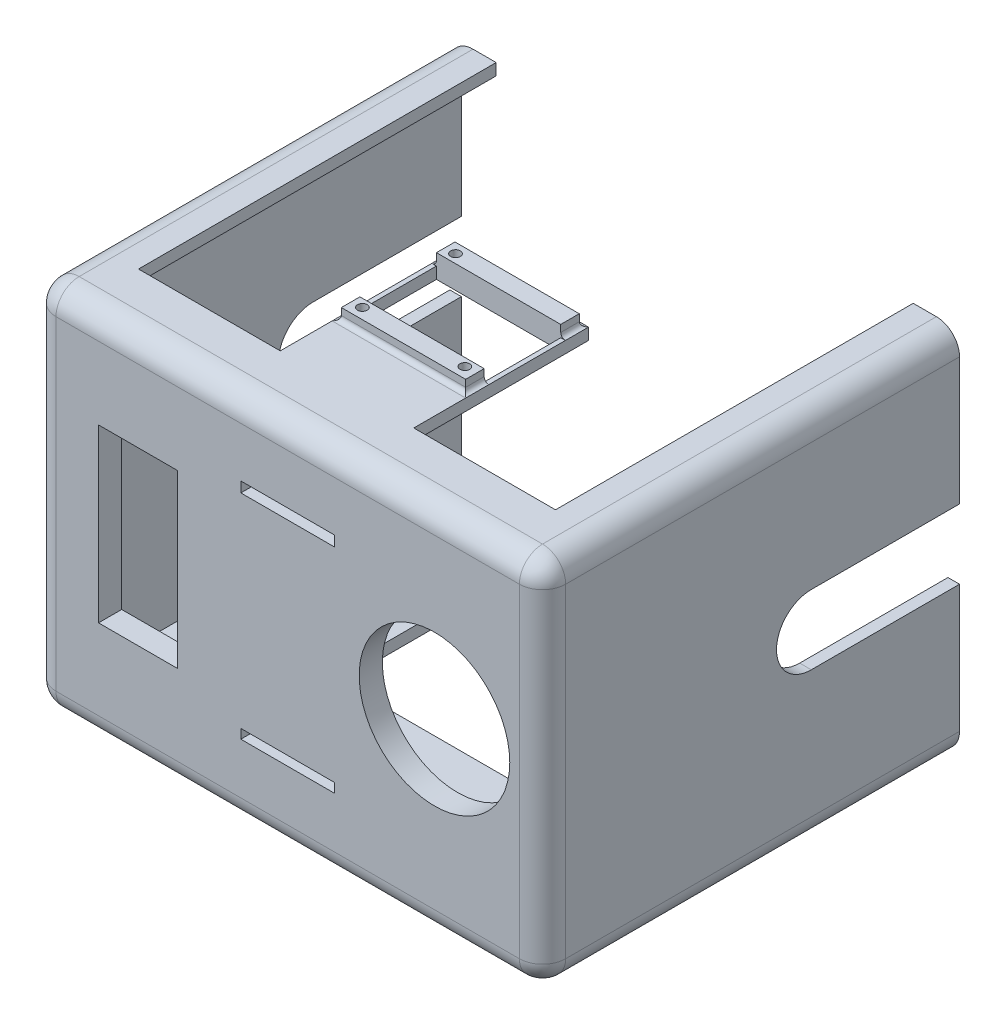
SolidWorks part; units mm, degrees
ref_plane "Plan de face" through (0, 0, 0) normal (0, 0, 1) x (1, 0, 0)
ref_plane "Plan de dessus" through (0, 0, 0) normal (0, 1, 0) x (1, 0, 0)
ref_plane "Plan de droite" through (0, 0, 0) normal (1, 0, 0) x (0, 0, -1)
sketch "Esquisse1" plane through (0, 0, 0) normal (0, 1, 0) x (1, 0, 0)
  line L1 (-48.5287, 46.8615) -> (61.4713, 46.8615)
  line L2 (-48.5287, 46.8615) -> (-48.5287, -53.1385)
  line L3 (-48.5287, -53.1385) -> (61.4713, -53.1385)
  line L4 (61.4713, 46.8615) -> (61.4713, -53.1385)
  point P10 (-45.5809, 46.8615)
  point P11 (-10.7604, 46.8615)
  point P12 (-6.0287, 46.8615)
  point P13 (13.9713, 46.8615)
  point P14 (27.7429, 46.8615)
  point P15 (44.6509, 46.8615)
  dimension "D1" = 100
  dimension "D2" = 110
extrude "Boss.-Extru.1" add sketch "Esquisse1" along normal blind 80
sketch "Esquisse3" plane through (0, 0, -46.8615) normal (0, 0, -1) x (-1, 0, 0)
  line L0 (-61.4713, 80) -> (-61.4713, 0) construction
  line L1 (-58.9713, 77.5) -> (46.0287, 77.5)
  line L2 (-58.9713, 77.5) -> (-58.9713, 2.5)
  line L3 (-58.9713, 2.5) -> (46.0287, 2.5)
  line L4 (46.0287, 77.5) -> (46.0287, 2.5)
  line L5 (-61.4713, 0) -> (48.5287, 0) construction
  dimension "D1" = 75
  dimension "D2" = 105
  dimension "D3" = 2.5
  dimension "D4" = 2.5
extrude "Enlèv. mat.-Extru.1" cut sketch "Esquisse3" against normal blind 95
sketch "Esquisse4" plane through (0, 0, 53.1385) normal (0, 0, 1) x (1, 0, 0)
  line L0 (-34.3516, 59.3625) -> (-17.3516, 59.3625)
  line L1 (-34.3516, 59.3625) -> (-34.3516, 22.3625)
  line L2 (-34.3516, 22.3625) -> (-17.3516, 22.3625)
  line L3 (-17.3516, 59.3625) -> (-17.3516, 22.3625)
  line L4 (-3.6381, 62.0051) -> (16.5807, 62.0051)
  line L5 (-3.6381, 62.0051) -> (-3.6381, 64.2449)
  line L6 (-3.6381, 64.2449) -> (16.5807, 64.2449)
  line L7 (16.5807, 62.0051) -> (16.5807, 64.2449)
  line L8 (-3.6393, 15.9751) -> (16.5807, 15.9751)
  line L9 (-3.6393, 15.9751) -> (-3.6393, 17.9949)
  line L10 (-3.6393, 17.9949) -> (16.5807, 17.9949)
  line L11 (16.5807, 15.9751) -> (16.5807, 17.9949)
  line L12 (-48.5287, 0) -> (61.4713, 0) construction
  line L13 (6.4713, 62.0051) -> (6.4713, 17.9949) construction
  line L15 (-48.5287, 80) -> (-48.5287, 0) construction
  line L16 (-48.5287, 40) -> (61.4713, 40) construction
  line L17 (61.4713, 80) -> (61.4713, 0) construction
  circle A0 centre (38.1549, 40.6366) radius 16.25
  point P18 (6.4713, 0)
  dimension "D1" = 32.5
extrude "Enlèv. mat.-Extru.2" cut sketch "Esquisse4" against normal through all
fillet "Congé2" radius 5 8 edges at (61.4713, 40, 53.1385) (61.4713, 80, 3.1385) (61.4713, 0, 3.1385) (6.4713, 80, 53.1385) (-48.5287, 80, 3.1385) (-48.5287, 40, 53.1385) (-48.5287, 0, 3.1385) (6.4713, 0, 53.1385)
sketch "Esquisse5" plane through (0, 0, 0) normal (0, -1, 0) x (1, 0, 0)
  line L0 (6.4713, -46.8615) -> (32.4713, -46.8615)
  line L1 (56.4713, -46.8615) -> (-43.5287, -46.8615) construction
  line L2 (6.4713, -46.8615) -> (-19.5287, -46.8615)
  line L3 (-19.5287, -46.8615) -> (-19.5287, 18.1385)
  line L4 (-19.5287, 18.1385) -> (32.4713, 18.1385)
  line L5 (32.4713, 18.1385) -> (32.4713, -46.8615)
  dimension "D1" = 26
  dimension "D2" = 26
  dimension "D3" = 65
extrude "Enlèv. mat.-Extru.3" cut sketch "Esquisse5" against normal blind 25
sketch "Esquisse6" plane through (-48.5287, 0, 0) normal (-1, 0, 0) x (0, 0, 1)
  line L0 (-46.8615, 40) -> (-4.8615, 40) construction
  line L1 (-46.8615, 75) -> (-46.8615, 5) construction
  line L2 (-4.8615, 47.5) -> (-46.8615, 47.5)
  line L3 (-4.8615, 32.5) -> (-46.8615, 32.5)
  line L4 (-46.8615, 47.5) -> (-46.8615, 32.5)
  arc A0 (-4.8615, 32.5) -> (-4.8615, 47.5) centre (-4.8615, 40) ccw
  dimension "D2" = 15
  dimension "D1" = 42
extrude "Enlèv. mat.-Extru.4" cut sketch "Esquisse6" against normal through all
sketch "Esquisse7" plane through (0, 0, 0) normal (0, -1, 0) x (1, 0, 0)
  line L1 (-48.5287, -46.8615) -> (61.4713, -46.8615)
  line L2 (-48.5287, -46.8615) -> (-48.5287, -36.8615)
  line L3 (-48.5287, -36.8615) -> (61.4713, -36.8615)
  line L4 (61.4713, -46.8615) -> (61.4713, -36.8615)
  dimension "D1" = 10
extrude "Enlèv. mat.-Extru.5" cut sketch "Esquisse7" against normal through all
sketch "Esquisse8" plane through (0, 80, 0) normal (0, 1, 0) x (1, 0, 0)
  line L0 (6.4713, -48.1385) -> (6.4713, -24.1385) construction
  line L32 (17.4061, -25.8459) -> (16.3561, -25.8459) construction
  line L37 (-6.9403, -28.1385) -> (19.8828, -28.1385)
  line L38 (-6.9403, -28.1385) -> (-6.9403, -24.1385)
  line L39 (-6.9403, -3.6192) -> (19.8828, -3.6192)
  line L40 (19.8828, -28.1385) -> (19.8828, -24.1385)
  line L41 (2.4066, -3.6192) -> (2.4066, -7.6192) construction
  line L42 (-43.5287, -48.1385) -> (56.4713, -48.1385) construction
  line L43 (56.4713, 36.8615) -> (-43.5287, 36.8615) construction
  line L44 (2.4066, -7.6192) -> (19.8828, -7.6192)
  line L45 (2.4066, -7.6192) -> (-6.9403, -7.6192)
  line L46 (-3.6439, -25.8459) -> (-4.6939, -25.8459) construction
  line L47 (2.4066, -28.1385) -> (2.4066, -24.1385) construction
  line L48 (2.4066, -24.1385) -> (19.8828, -24.1385)
  line L49 (2.4066, -24.1385) -> (-6.9403, -24.1385)
  line L50 (-6.9403, -7.6192) -> (-6.9403, -3.6192)
  line L51 (6.4713, -7.6192) -> (6.4713, 36.8615) construction
  line L52 (19.8828, -7.6192) -> (19.8828, -3.6192)
  circle A5 centre (17.4061, -25.8459) radius 1.05
  circle A6 centre (-4.6939, -25.8459) radius 1.05
  circle A7 centre (-4.6939, -5.7459) radius 1.05
  point P7 (6.4713, -28.1385)
  dimension "D2" = 2.1
  dimension "D3" = 2.1
  dimension "D4" = 2.1
  dimension "D1" = 20
extrude "Boss.-Extru.4" add sketch "Esquisse8" along normal blind 2.5
sketch "Esquisse12" plane through (0, 80, 0) normal (0, 1, 0) x (1, 0, 0)
  line L1 (-6.9403, -7.6192) -> (19.8828, -7.6192)
  line L2 (-6.9403, -7.6192) -> (-6.9403, -24.1385)
  line L3 (-6.9403, -24.1385) -> (19.8828, -24.1385)
  line L4 (19.8828, -7.6192) -> (19.8828, -24.1385)
extrude "Enlèv. mat.-Extru.8" cut sketch "Esquisse12" against normal blind 2.5
fillet "Congé3" radius 1 6 edges at (-6.9403, 80, 5.6192) (19.8828, 80, 5.6192) (6.4713, 80, 3.6192) (19.8828, 80, 26.1385) (6.4713, 80, 28.1385) (-6.9403, 80, 26.1385)
sketch "Esquisse13" plane through (0, 80, 0) normal (0, 1, 0) x (1, 0, 0)
  line L0 (-43.5287, 36.8615) -> (-43.5287, -48.1385) construction
  line L1 (-38.5287, 36.8615) -> (51.4713, 36.8615)
  line L2 (-38.5287, 36.8615) -> (-38.5287, -2.6192)
  line L3 (-7.9403, -2.6192) -> (20.8828, -2.6192)
  line L4 (51.4713, 36.8615) -> (51.4713, -2.6192)
  line L5 (56.4713, 36.8615) -> (-43.5287, 36.8615) construction
  line L6 (-7.9403, -2.6192) -> (20.8828, -2.6192) construction
  line L9 (-38.5287, -2.6192) -> (-38.5287, -40.3321)
  line L10 (-38.5287, -40.3321) -> (-7.9403, -40.3321)
  line L11 (-7.9403, -2.6192) -> (-7.9403, -40.3321)
  line L13 (51.4713, -2.6192) -> (51.4713, -40.3321)
  line L14 (51.4713, -40.3321) -> (20.8828, -40.3321)
  line L15 (20.8828, -2.6192) -> (20.8828, -40.3321)
  dimension "D1" = 90
  dimension "D2" = 5
  dimension "D3" = 0
  dimension "D4" = 0
extrude "Enlèv. mat.-Extru.9" cut sketch "Esquisse13" against normal blind 10
